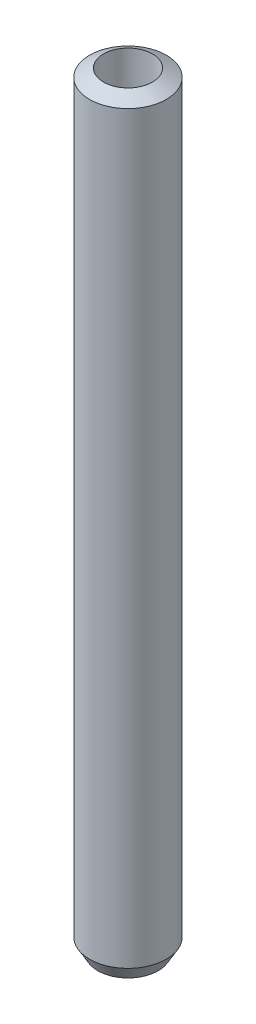
SolidWorks part; units mm, degrees
ref_plane "Front Plane" through (0, 0, 0) normal (0, 0, 1) x (1, 0, 0)
ref_plane "Top Plane" through (0, 0, 0) normal (0, 1, 0) x (1, 0, 0)
ref_plane "Right Plane" through (0, 0, 0) normal (1, 0, 0) x (0, 0, -1)
sketch "Sketch1" plane through (0, 0, 0) normal (0, 1, 0) x (1, 0, 0)
  circle A0 centre (0, 0) radius 15
  dimension "SHAFT_OD" = 30
extrude "Boss-Extrude1" add sketch "Sketch1" along normal blind 299.7171
sketch "Sketch2" plane through (0, 0, 0) normal (0, 1, 0) x (1, 0, 0)
  circle A0 centre (0, 0) radius 9.5556
  dimension "BORE_D" = 19.1112
extrude "Cut-Extrude1" cut sketch "Sketch2" along normal through all
chamfer "Chamfer1" distance 3.1861 angle 60 2 edges at (0, 299.7171, 15) (0, 0, 15) first distance on face at (0, 299.7171, 15) first distance on face at (0, 0, 9.5556)
